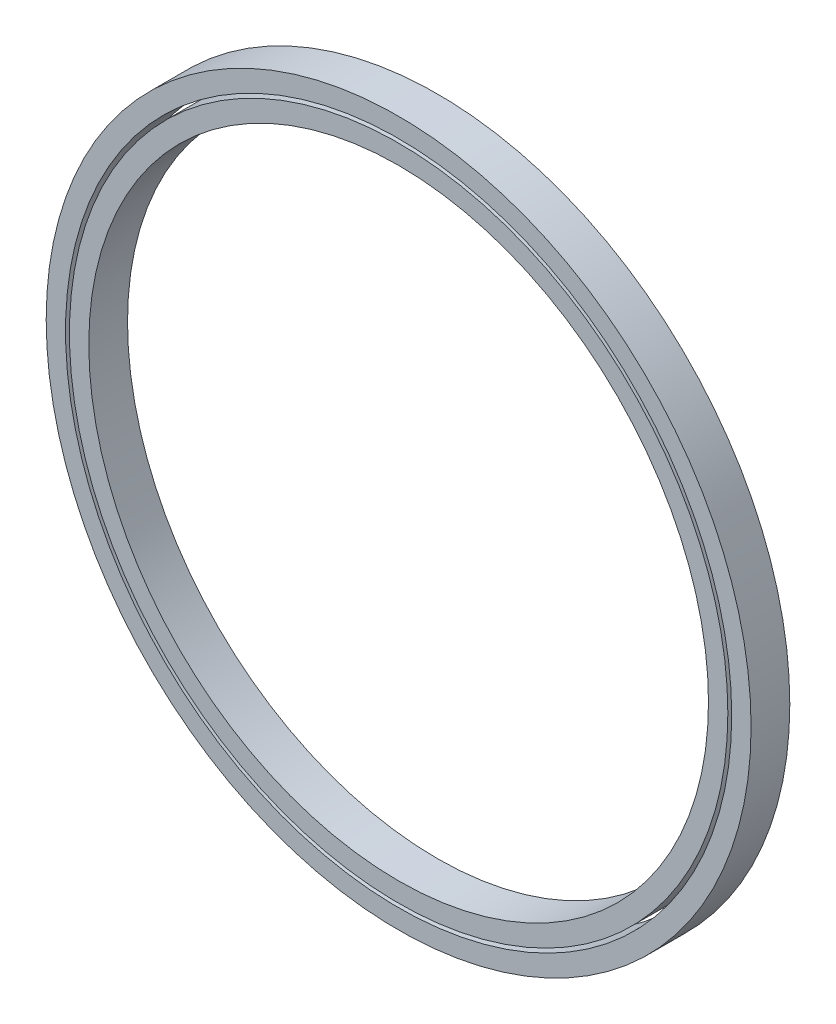
SolidWorks part; units mm, degrees
material "Plain Carbon Steel"
ref_plane "XY" through (0, 0, 0) normal (0, 0, 1) x (1, 0, 0)
ref_plane "XZ" through (0, 0, 0) normal (0, 1, 0) x (1, 0, 0)
ref_plane "YZ" through (0, 0, 0) normal (1, 0, 0) x (0, 0, -1)
sketch "Sketch1" plane through (0, 0, 0) normal (0, 0, 1) x (1, 0, 0)
  line L0 (40, 0) -> (45.5, 0) construction
  line L1 (42.5, 0) -> (43, 0) construction
  circle A0 centre (0, 0) radius 40
  circle A1 centre (0, 0) radius 42.5
  circle A2 centre (0, 0) radius 43
  circle A3 centre (0, 0) radius 45.5
  point P10 (42.75, 0)
  dimension "D1" = 80
  dimension "D2" = 5.5
  dimension "D3" = 0.5
extrude "Boss-Extrude1" add sketch "Sketch1" along normal mid plane 5 contours A1 A0 | A3 A2 region at (-41.2979, 0, 0) region at (-44.2131, 0, 0)
